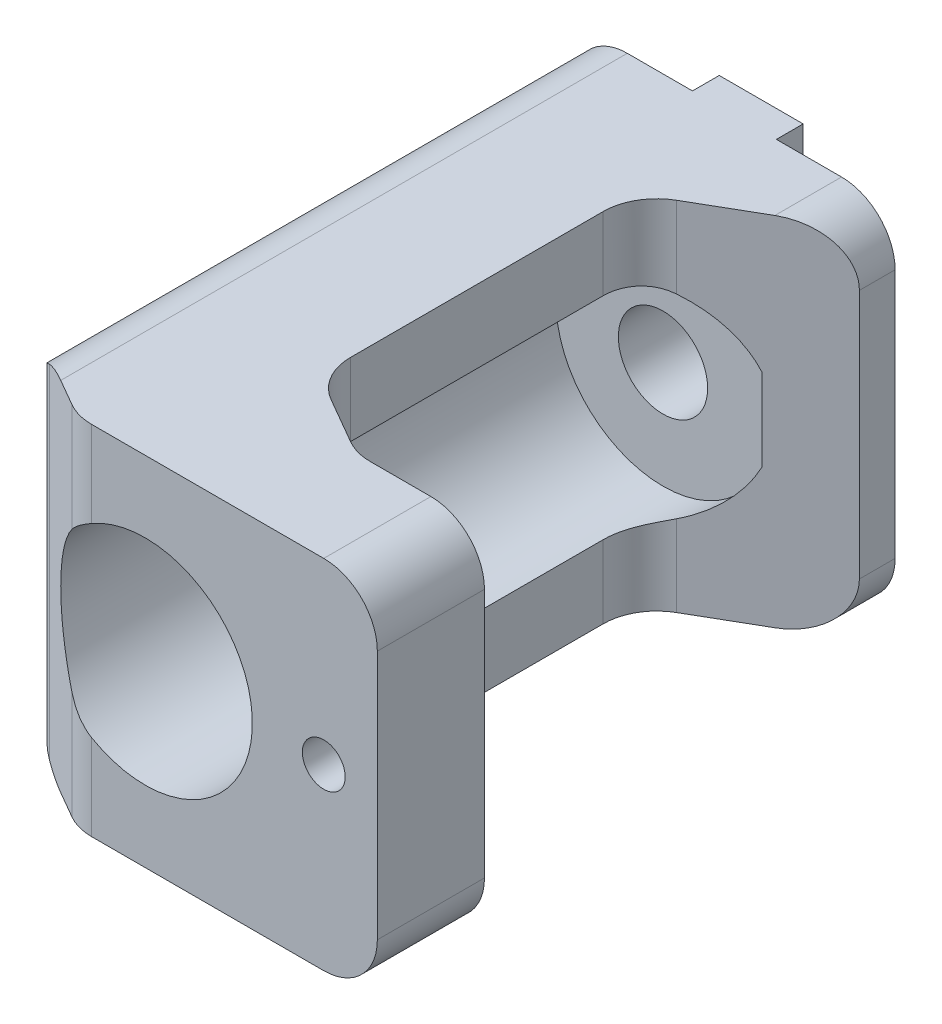
SolidWorks part; units mm, degrees
material "ABS"
ref_plane "Plan de face" through (0, 0, 0) normal (0, 0, 1) x (1, 0, 0)
ref_plane "Plan de dessus" through (0, 0, 0) normal (0, 1, 0) x (1, 0, 0)
ref_plane "Plan de droite" through (0, 0, 0) normal (1, 0, 0) x (0, 0, -1)
sketch "Esquisse1" plane through (0, 0, 0) normal (0, 1, 0) x (1, 0, 0)
  line L0 (2.35, 0) -> (9, 0)
  line L1 (-2.35, 1.5) -> (2.35, 1.5)
  line L2 (-2.35, 1.5) -> (-2.35, 0)
  line L3 (-2.35, 0) -> (2.35, 0) construction
  line L4 (2.35, 1.5) -> (2.35, 0)
  line L5 (-9, 0) -> (-2.35, 0)
  line L6 (-9, 0) -> (-9, -25)
  line L7 (1, -25) -> (-9, -25)
  line L8 (9, -2) -> (1, -6.6188)
  line L9 (1, -6.6188) -> (1, -25)
  line L10 (9, -2) -> (9, 0)
  dimension "D1" = 9
  dimension "D2" = 25
  dimension "D3" = 2
  dimension "D4" = 4.7
  dimension "D5" = 1.5
  dimension "D6" = 30
  dimension "D7" = 1
extrude "Boss.-Extru.1" add sketch "Esquisse1" along normal mid plane 20
sketch "Esquisse2" plane through (-1.3724, 0, 0) normal (0, 0, 1) x (1, 0, 0)
  circle A0 centre (1.3724, 0) radius 2.5
  dimension "D1" = 5
extrude "Enlèv. mat.-Extru.1" cut sketch "Esquisse2" against normal through all both and the other way through all
sketch "Esquisse3" plane through (0, 0, 0) normal (0, 0, 1) x (1, 0, 0)
  circle A0 centre (0, 0) radius 6
  dimension "D1" = 12
extrude "Enlèv. mat.-Extru.2" cut sketch "Esquisse3" along normal through all from offset 4
sketch "Esquisse5" plane through (-2.35, 0, 0) normal (-1, 0, 0) x (0, 0, 1)
  line L0 (-1.5, 10) -> (-1.5, 0.8529) construction
  line L1 (-1.5, 2) -> (0, 2)
  line L2 (-1.5, 2) -> (-1.5, -2)
  line L3 (-1.5, -2) -> (0, -2)
  line L4 (0, 2) -> (0, -2)
  dimension "D1" = 4
extrude "Enlèv. mat.-Extru.3" cut sketch "Esquisse5" against normal through all
sketch "Esquisse6" plane through (0, 10, 0) normal (0, 1, 0) x (1, 0, 0)
  line L0 (-9, -18.453) -> (5.8038, -27)
  line L1 (-9, 0) -> (-9, -25) construction
  line L2 (5.8038, -27) -> (13, -27)
  line L3 (13, -27) -> (13, -33)
  line L4 (13, -33) -> (-3.8038, -33)
  line L5 (-3.8038, -33) -> (-9, -30)
  line L6 (-9, -30) -> (-9, -18.453)
  line L7 (9, 0) -> (2.35, 0) construction
  line L8 (-2.35, 0) -> (-9, 0) construction
  dimension "D1" = 6
  dimension "D2" = 33
  dimension "D3" = 13
  dimension "D4" = 30
  dimension "D5" = 30
  dimension "D6" = 10
extrude "Boss.-Extru.2" add sketch "Esquisse6" against normal up to surface (20 mm away) up to face at (0.2, -10, 5.5619)
sketch "Esquisse7" plane through (0, 0, 33) normal (0, 0, 1) x (1, 0, 0)
  circle A0 centre (10, 0) radius 1.2
  circle A1 centre (0, 0) radius 6 construction
  circle A2 centre (0, 0) radius 6
  dimension "D1" = 2.4
  dimension "D2" = 10
extrude "Enlèv. mat.-Extru.4" cut sketch "Esquisse7" against normal blind 20
fillet "Congé1" radius 3 15 edges at (-9, -10, 15) (-9, 10, 15) (9, -10, 1) (9, 10, 1) (13, -10, 30) (13, 10, 30) (5.8038, 5.7608, 27) (5.8038, -5.7608, 27) (-3.8038, -7.3201, 33) (-3.8038, 7.3201, 33) (-9, 0, 30) (1, -7.958, 24.2265) (1, -7.958, 6.6188) (1, 7.958, 6.6188) (1, 7.958, 24.2265)
